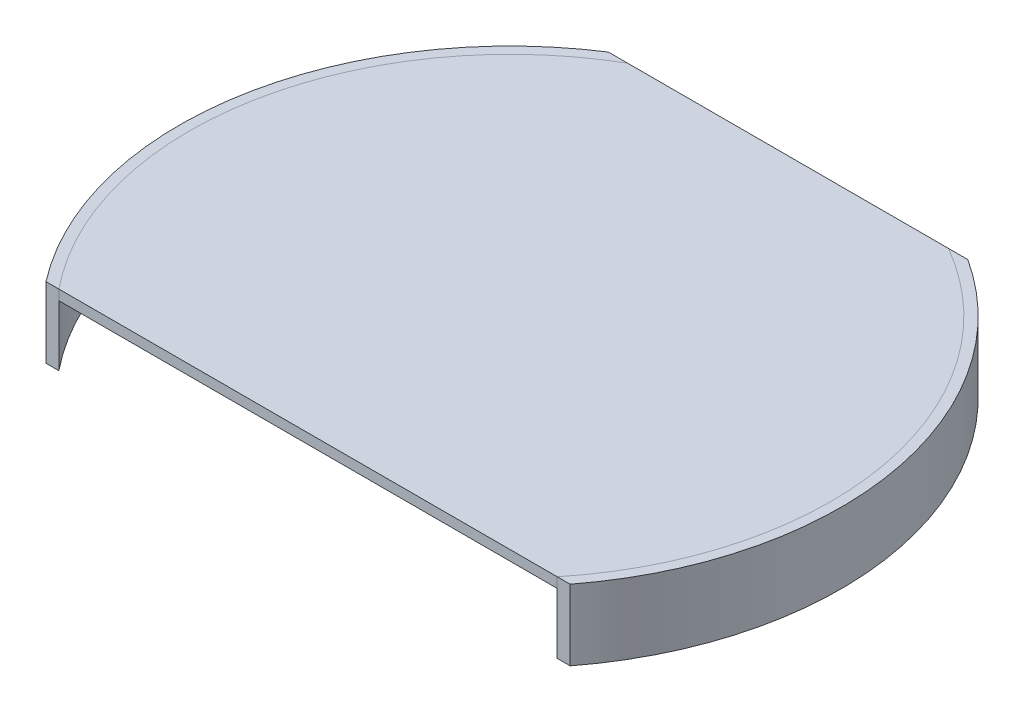
SolidWorks part; units mm, degrees
ref_plane "Front Plane" through (0, 0, 0) normal (0, 0, 1) x (1, 0, 0)
ref_plane "Top Plane" through (0, 0, 0) normal (0, 1, 0) x (1, 0, 0)
ref_plane "Right Plane" through (0, 0, 0) normal (1, 0, 0) x (0, 0, -1)
sketch "Sketch1" plane through (0, 0, 0) normal (0, 1, 0) x (1, 0, 0)
  line L0 (0, 0) -> (0, -40) construction
  line L1 (-49.3178, -40) -> (49.3178, -40)
  line L2 (31.7372, 55) -> (-31.7372, 55)
  line L3 (0, 0) -> (0, 55) construction
  arc A0 (49.3178, -40) -> (31.7372, 55) centre (0, 0) ccw
  arc A1 (-49.3178, -40) -> (49.3178, -40) centre (0, 0) ccw construction
  arc A2 (31.7372, 55) -> (-31.7372, 55) centre (0, 0) ccw construction
  arc A3 (-31.7372, 55) -> (-49.3178, -40) centre (0, 0) ccw
  dimension "D1" = 127
  dimension "D2" = 40
  dimension "D3" = 55
extrude "Boss-Extrude1" add sketch "Sketch1" along normal blind 2
sketch "Sketch3" plane through (0, 0, 0) normal (0, -1, 0) x (1, 0, 0)
  line L0 (0, 0) -> (0, -55) construction
  line L1 (31.7372, -55) -> (-31.7372, -55) construction
  line L2 (31.7372, -55) -> (35.5704, -55)
  line L3 (49.3178, 40) -> (51.8676, 40)
  line L4 (51.8676, 40) -> (53.151, 40) construction
  line L5 (-31.7372, -55) -> (-35.5704, -55)
  line L6 (-49.3178, 40) -> (-51.8676, 40)
  arc A0 (31.7372, -55) -> (49.3178, 40) centre (0, 0) ccw
  arc A1 (31.7372, -55) -> (49.3178, 40) centre (0, 0) ccw construction
  arc A3 (35.5704, -55) -> (51.8676, 40) centre (0, 0) ccw
  arc A4 (-31.7372, -55) -> (-49.3178, 40) centre (0, 0) cw
  arc A5 (-35.5704, -55) -> (-51.8676, 40) centre (0, 0) cw
  dimension "D1" = 2
extrude "Boss-Extrude2" add sketch "Sketch3" along normal blind 12 and the other way up to surface (2 mm away) separate body other way up to face at (0, 2, -9.5275)
